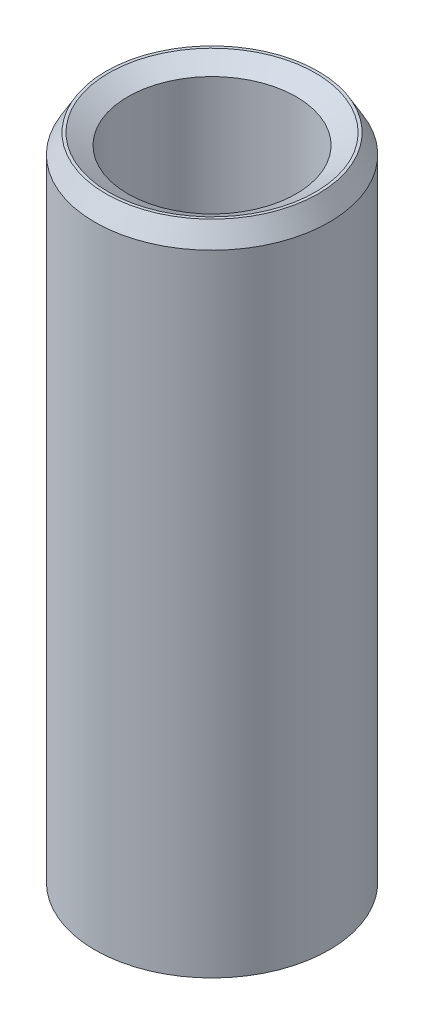
SolidWorks part; units mm, degrees
ref_plane "Front Plane" through (0, 0, 0) normal (0, 0, 1) x (1, 0, 0)
ref_plane "Top Plane" through (0, 0, 0) normal (0, 1, 0) x (1, 0, 0)
ref_plane "Right Plane" through (0, 0, 0) normal (1, 0, 0) x (0, 0, -1)
sketch "Sketch1" plane through (0, 0, 0) normal (0, 1, 0) x (1, 0, 0)
  circle A0 centre (0, 0) radius 10
  dimension "SLEEVE_OD" = 20
extrude "Boss-Extrude1" add sketch "Sketch1" along normal blind 56.364
sketch "Sketch2" plane through (0, 0, 0) normal (0, 1, 0) x (1, 0, 0)
  circle A0 centre (0, 0) radius 7.1854
  dimension "BORE_D" = 14.3708
extrude "Cut-Extrude1" cut sketch "Sketch2" along normal through all
chamfer "Chamfer1" distance 1.6311 angle 30 4 edges at (0, 56.364, 7.1854) (0, 0, 7.1854) (0, 0, 10) (0, 56.364, 10) first distance on face at (0, 56.364, 7.1854) first distance on face at (0, 0, 7.1854) first distance on face at (0, 56.364, 10)
